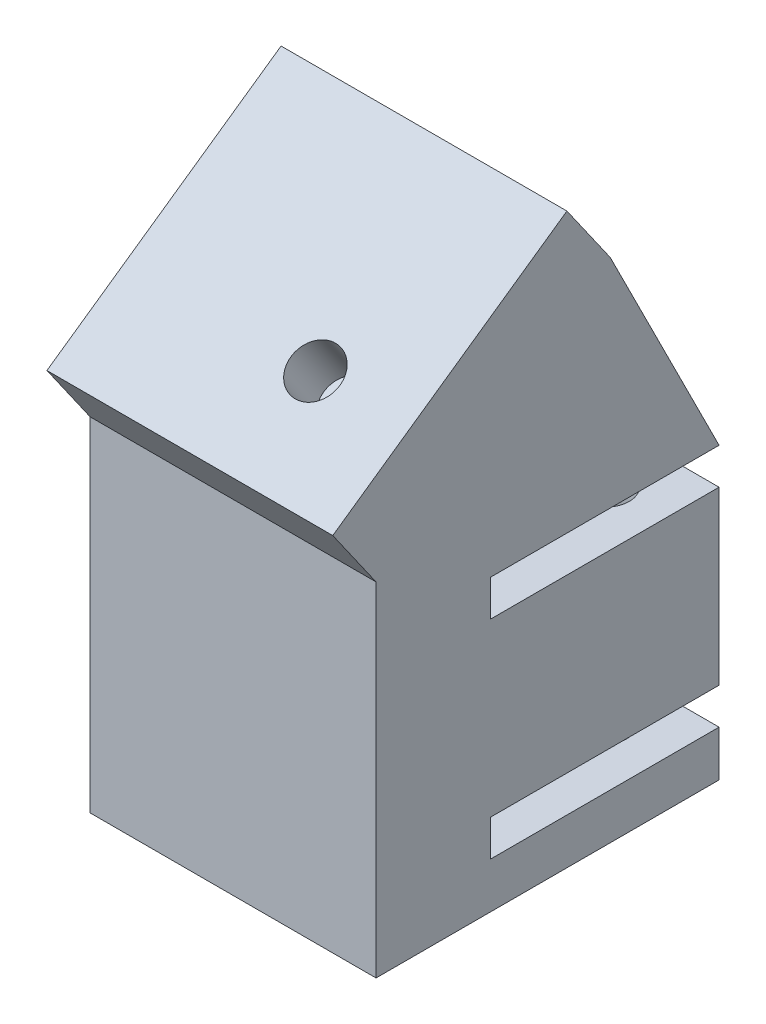
SolidWorks part; units mm, degrees
ref_plane "Front Plane" through (0, 0, 0) normal (0, 0, 1) x (1, 0, 0)
ref_plane "Top Plane" through (0, 0, 0) normal (0, 1, 0) x (1, 0, 0)
ref_plane "Right Plane" through (0, 0, 0) normal (1, 0, 0) x (0, 0, -1)
sketch "Sketch1" plane through (0, 0, 0) normal (1, 0, 0) x (0, 0, -1)
  line L0 (20, 0) -> (0, 0)
  line L1 (20, 0) -> (20, -15)
  line L2 (20, -15) -> (0, -15)
  line L3 (0, -15) -> (0, -18.175)
  line L4 (0, -18.175) -> (20, -18.175)
  line L5 (20, -18.175) -> (20, -22.175)
  line L6 (20, -22.175) -> (-10, -22.175)
  line L7 (-10, -22.175) -> (-10, 7.825)
  line L8 (-10, 7.825) -> (10.4788, 22.1644)
  line L10 (0, 0) -> (0, 3.175)
  line L11 (0, 3.175) -> (20, 3.175)
  line L12 (20, 3.175) -> (10.4788, 22.1644)
  dimension "D1" = 3.175
  dimension "D2" = 15
  dimension "D3" = 4
  dimension "D4" = 20
  dimension "D5" = 30
  dimension "D6" = 25
  dimension "D7" = 125
  dimension "D8" = 30
extrude "Boss-Extrude1" add sketch "Sketch1" along normal blind 25
sketch "Sketch2" plane through (0, 9.9491, 6.9664) normal (0, 0.8192, 0.5736) x (1, 0, 0)
  line L1 (0, 21.2967) -> (21, 21.2967)
  line L2 (0, 21.2967) -> (0, 0.2967)
  line L3 (0, 0.2967) -> (21, 0.2967)
  line L4 (21, 21.2967) -> (21, 0.2967)
  line L5 (0, 21.2967) -> (25, 21.2967)
  line L6 (0, 21.2967) -> (0, -3.7033)
  line L7 (0, -3.7033) -> (25, -3.7033)
  line L8 (25, 21.2967) -> (25, -3.7033)
  line M5 (0, 21.2967) -> (0, -3.7033)
  line M6 (0, -3.7033) -> (25, -3.7033)
  line M7 (25, -3.7033) -> (25, 21.2967)
  line M8 (25, 21.2967) -> (0, 21.2967)
  dimension "D1" = 4
  dimension "D2" = 4
extrude "Boss-Extrude2" add sketch "Sketch2" along normal blind 1.6 contours L4 L3 M8 M5 M6 M7 region at (23, 21.9616, -10.1892)
sketch "Sketch3" plane through (0, 11.2598, 7.8842) normal (0, 0.8192, 0.5736) x (1, 0, 0)
  line L1 (25, -3.7033) -> (0, -3.7033)
  line L2 (25, -3.7033) -> (25, 21.2967)
  line L3 (25, 21.2967) -> (0, 21.2967)
  line L4 (0, -3.7033) -> (0, 21.2967)
extrude "Boss-Extrude3" add sketch "Sketch3" along normal blind 5
sketch "Sketch4" plane through (0, 15.3555, 10.7521) normal (0, 0.8192, 0.5736) x (1, 0, 0)
  line L0 (25, -3.7033) -> (25, 21.2967) construction
  line L1 (0, -3.7033) -> (25, -3.7033) construction
  circle A0 centre (16.6, 4.6967) radius 2.15
  dimension "D1" = 4.3
  dimension "D2" = 8.4
  dimension "D3" = 8.4
extrude "Cut-Extrude1" cut sketch "Sketch4" against normal up to surface (5 mm away) up to face at (10.5, 17.4525, -0.96)
sketch "Sketch5" plane through (0, 15.3555, 10.7521) normal (0, 0.8192, 0.5736) x (1, 0, 0)
  circle A0 centre (16.6, 4.6967) radius 1.85
  dimension "D1" = 3.7
extrude "Cut-Extrude2" cut sketch "Sketch5" against normal blind 13
sketch "Sketch6" plane through (0, -18.175, 0) normal (0, 1, 0) x (1, 0, 0)
  line L0 (0, 20) -> (0, 10.4788) construction
  line L1 (25, 20) -> (0, 20) construction
  line L2 (25, 20) -> (25, 10.4788) construction
  circle A0 centre (5, 15) radius 1.85
  circle A1 centre (20, 15) radius 1.85
  dimension "D1" = 3.7
  dimension "D2" = 3.7
  dimension "D3" = 5
  dimension "D4" = 5
  dimension "D5" = 5
  dimension "D6" = 5
extrude "Cut-Extrude3" cut sketch "Sketch6" against normal blind 13
sketch "Sketch7" plane through (0, -15, 0) normal (0, -1, 0) x (1, 0, 0)
  circle A0 centre (5, -15) radius 2.15
  circle A1 centre (20, -15) radius 2.15
  dimension "D1" = 4.3
extrude "Cut-Extrude4" cut sketch "Sketch7" against normal blind 43
sketch "Sketch8" plane through (0, 0, 0) normal (0, 1, 0) x (1, 0, 0)
  circle A0 centre (5, 15) radius 4
  circle A1 centre (20, 15) radius 4
  dimension "D1" = 8
extrude "Cut-Extrude5" cut sketch "Sketch8" along normal blind 67 from offset 7
equation "\"D2@Sketch6\"=\"D1@Sketch6\""
